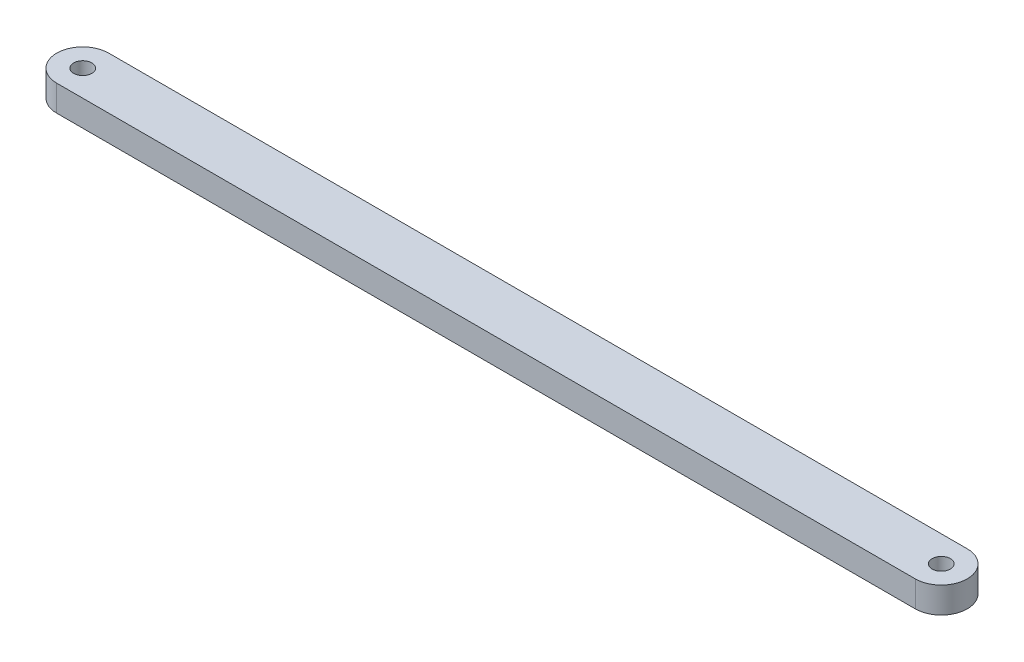
SolidWorks part; units mm, degrees
ref_plane "Front Plane" through (0, 0, 0) normal (0, 0, 1) x (1, 0, 0)
ref_plane "Top Plane" through (0, 0, 0) normal (0, 1, 0) x (1, 0, 0)
ref_plane "Right Plane" through (0, 0, 0) normal (1, 0, 0) x (0, 0, -1)
sketch "Sketch1" plane through (0, 0, 0) normal (0, 1, 0) x (1, 0, 0)
  line L0 (-165, 0) -> (165, 0) construction
  line L4 (-165, 10) -> (165, 10)
  line L5 (-165, -10) -> (165, -10)
  arc A3 (-165, 10) -> (-165, -10) centre (-165, 0) ccw
  arc A4 (165, -10) -> (165, 10) centre (165, 0) ccw
  circle A5 centre (-165, 0) radius 3.5
  circle A6 centre (165, 0) radius 3.5
  point P2 (0, 0)
  dimension "D3" = 7
  dimension "D4" = 7
  dimension "D1" = 20
  dimension "D2" = 330
extrude "Boss-Extrude1" add sketch "Sketch1" along normal blind 10
equation "\"D2@Sketch1\"=165+165"
